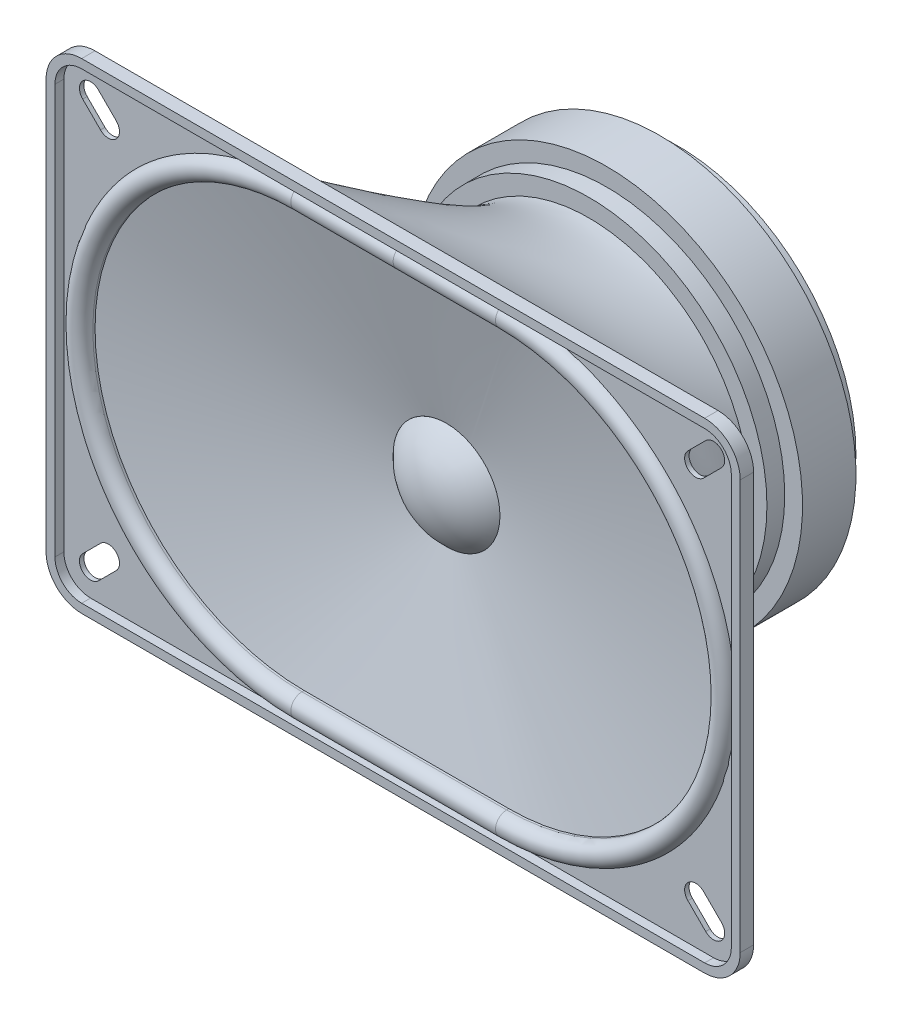
SolidWorks part; units mm, degrees
note: '?' marks a value the reader was unsure of.
ref_plane "Front Plane" through (0, 0, 0) normal (0, 0, 1) x (1, 0, 0)
ref_plane "Top Plane" through (0, 0, 0) normal (0, 1, 0) x (1, 0, 0)
ref_plane "Right Plane" through (0, 0, 0) normal (1, 0, 0) x (0, 0, -1)
sketch "Sketch1" plane through (0, 0, 0) normal (0, 0, 1) x (1, 0, 0)
  line L1 (-61.9125, -42.8625) -> (61.9125, -42.8625)
  line L2 (-61.9125, -42.8625) -> (-61.9125, 42.8625)
  line L3 (-61.9125, 42.8625) -> (61.9125, 42.8625)
  line L4 (61.9125, -42.8625) -> (61.9125, 42.8625)
  line L5 (-61.9125, -42.8625) -> (61.9125, 42.8625) construction
  line L6 (-61.9125, 42.8625) -> (61.9125, -42.8625) construction
  point P0 (0, 0)
  dimension "D1" = 123.825
  dimension "D2" = 85.725
extrude "Boss-Extrude1" add sketch "Sketch1" along normal blind 2.3813
fillet "Fillet1" radius 6.35 4 edges at (-61.9125, -42.8625, 1.1906) (61.9125, -42.8625, 1.1906) (61.9125, 42.8625, 1.1906) (-61.9125, 42.8625, 1.1906)
sketch "Sketch2" plane through (0, 0, 2.3813) normal (0, 0, 1) x (1, 0, 0)
  line L8 (-60.325, 36.5125) -> (-60.325, -36.5125)
  line L9 (-55.5625, -41.275) -> (55.5625, -41.275)
  line L10 (60.325, -36.5125) -> (60.325, 36.5125)
  line L11 (55.5625, 41.275) -> (-55.5625, 41.275)
  line L12 (-60.325, 36.5125) -> (-60.325, -36.5125)
  line L13 (-55.5625, -41.275) -> (55.5625, -41.275)
  line L14 (60.325, -36.5125) -> (60.325, 36.5125)
  line L15 (55.5625, 41.275) -> (-55.5625, 41.275)
  arc A8 (-60.325, -36.5125) -> (-55.5625, -41.275) centre (-55.5625, -36.5125) ccw
  arc A9 (55.5625, -41.275) -> (60.325, -36.5125) centre (55.5625, -36.5125) ccw
  arc A10 (60.325, 36.5125) -> (55.5625, 41.275) centre (55.5625, 36.5125) ccw
  arc A11 (-55.5625, 41.275) -> (-60.325, 36.5125) centre (-55.5625, 36.5125) ccw
  arc A12 (-60.325, -36.5125) -> (-55.5625, -41.275) centre (-55.5625, -36.5125) ccw
  arc A13 (55.5625, -41.275) -> (60.325, -36.5125) centre (55.5625, -36.5125) ccw
  arc A14 (60.325, 36.5125) -> (55.5625, 41.275) centre (55.5625, 36.5125) ccw
  arc A15 (-55.5625, 41.275) -> (-60.325, 36.5125) centre (-55.5625, 36.5125) ccw
  dimension "D1" = 1.5875
extrude "Cut-Extrude1" cut sketch "Sketch2" against normal blind 1.5875
sketch "Sketch3" plane through (0, 0, 0.7938) normal (0, 0, 1) x (1, 0, 0)
  line L0 (-18.2563, 0) -> (18.2563, 0) construction
  line L1 (29.6862, 0) -> (-29.6862, 0) construction
  line L2 (-18.2563, 38.8937) -> (18.2563, 38.8937)
  line L3 (-18.2563, -38.8937) -> (18.2563, -38.8937)
  line L4 (0, 0) -> (0, 56.4143) construction
  line L5 (0, -55) -> (0, 55) construction
  arc A0 (-18.2563, 38.8937) -> (-18.2563, -38.8937) centre (-18.2563, 0) ccw
  arc A1 (18.2563, -38.8937) -> (18.2563, 38.8937) centre (18.2563, 0) ccw
  point P5 (0, 0)
  dimension "D2" = 114.3
  dimension "D1" = 77.7875
extrude "Cut-Extrude2" cut sketch "Sketch3" against normal up to next
ref_plane "Plane1" through (0, 0, -48.4187) normal (0, 0, 1) x (1, 0, 0)
sketch "Sketch5" plane through (0, 0, 0) normal (1, 0, 0) x (0, 0, -1)
  line L0 (0, 0) -> (61.7456, 0) construction
  line L1 (29.6862, 0) -> (-29.6862, 0) construction
  line L2 (48.4187, 0) -> (48.4187, 9.525)
  line L3 (48.4187, 47.1487) -> (48.4187, -47.1487) construction
  line L4 (48.4187, 9.525) -> (7.1437, 9.525)
  line L5 (2.844, 0) -> (2.844, 33.6301) construction
  line L6 (2.844, 0) -> (48.4187, 0)
  arc A0 (2.844, 0) -> (7.1437, 9.525) centre (15.544, 0) cw
  dimension "D2" = 12.7
  dimension "D1" = 9.525
  dimension "D3" = 41.275
revolve "Revolve1" add sketch "Sketch5" angle 360 about L0
sketch "Sketch6" plane through (0, 0, -48.4187) normal (0, 0, 1) x (1, 0, 0)
  circle A0 centre (0, 0) radius 31.75
  dimension "D1" = 63.5
extrude "Boss-Extrude2" add sketch "Sketch6" along normal blind 15.875
ref_axis "Axis1" through (0, 0, -32.5437) along (0, 0, 1)?
sketch "Sketch10" plane through (0, 0, 0) normal (0, 0, 1) x (1, 0, 0)
  line L4 (-18.2563, -37.3062) -> (18.2562, -37.3062)
  line L5 (18.2563, 37.3062) -> (-18.2563, 37.3062)
  line L6 (-18.2563, -37.3062) -> (18.2562, -37.3062)
  line L7 (18.2563, 37.3062) -> (-18.2563, 37.3062)
  arc A4 (18.2562, -37.3062) -> (18.2563, 37.3062) centre (18.2563, 0) ccw
  arc A5 (-18.2563, 37.3062) -> (-18.2563, -37.3062) centre (-18.2563, 0) ccw
  arc A6 (18.2562, -37.3062) -> (18.2563, 37.3062) centre (18.2563, 0) ccw
  arc A7 (-18.2563, 37.3062) -> (-18.2563, -37.3062) centre (-18.2563, 0) ccw
  dimension "D1" = 1.5875
ref_plane "Plane3" through (0, 0, -7.1437) normal (0, 0, 1) x (1, 0, 0)
sketch "Sketch11" plane through (0, 0, -7.1437) normal (0, 0, 1) x (1, 0, 0)
  line L0 (0, 0) -> (-18.2563, -37.3062) construction
  line L1 (-18.2563, 37.3062) -> (0, 0) construction
  line L2 (0, 0) -> (18.2563, 37.3062) construction
  line L3 (18.2562, -37.3062) -> (0, 0) construction
  arc A2 (-4.1867, -8.5555) -> (4.1867, -8.5555) centre (0, 0) ccw
  circle A3 centre (0, 0) radius 9.525 construction
  circle A4 centre (0, 0) radius 9.525 construction
  arc A5 (-4.1867, -8.5555) -> (-4.1867, 8.5555) centre (0, 0) cw
  arc A6 (-4.1867, 8.5555) -> (4.1867, 8.5555) centre (0, 0) cw
  arc A7 (4.1867, 8.5555) -> (4.1867, -8.5555) centre (0, 0) cw
ref_plane "Plane4" through (0, 0, 0) normal (-0.8982, 0.4396, 0) x (0, 0, 1)
other "Boundary-Surface1"
sketch "Sketch14" plane through (0, 0, 0) normal (1, 0, 0) x (0, 0, -1)
  line L0 (0, 37.2999) -> (-0.3937, 37.2999)
  line L1 (-0.3937, 41.275) -> (1.312, 41.275) construction
  line L2 (-2.3813, 42.8625) -> (-2.3813, 36.5125) construction
  line L3 (0, 47.1487) -> (0, -47.1487) construction
  line L4 (-2.3813, 42.8625) -> (0, 42.8625) construction
  line L6 (0, 37.8079) -> (-0.3937, 37.8079)
  line L7 (0, 37.2999) -> (0, 37.8079)
  line L8 (-0.3937, 41.275) -> (-0.3937, 40.767)
  arc A0 (-0.3937, 37.2999) -> (-0.3937, 41.275) centre (-0.3937, 39.2874) cw
  arc A1 (-0.3937, 37.8079) -> (-0.3937, 40.767) centre (-0.3937, 39.2874) cw
  dimension "D1" = 1.5875
  dimension "D3" = 5.5626
  dimension "D4" = 0.508
sketch "Sketch16" plane through (0, 0, 0) normal (0, 0, 1) x (1, 0, 0)
  line L0 (-18.2563, 37.3062) -> (18.2563, 37.3062) construction
  line L1 (18.2562, -37.3062) -> (-18.2563, -37.3062) construction
  line L2 (-18.2563, 37.3062) -> (18.2563, 37.3062)
  line L3 (18.2562, -37.3062) -> (-18.2563, -37.3062)
  arc A0 (18.2562, -37.3062) -> (18.2563, 37.3062) centre (18.2563, 0) ccw construction
  arc A1 (-18.2563, 37.3062) -> (-18.2563, -37.3062) centre (-18.2563, 0) ccw construction
  arc A2 (18.2562, -37.3062) -> (18.2563, 37.3062) centre (18.2563, 0) ccw
  arc A3 (-18.2563, 37.3062) -> (-18.2563, -37.3062) centre (-18.2563, 0) ccw
surface "Surface-Sweep1"
sketch "Sketch17" plane through (0, 0, -32.5437) normal (0, 0, 1) x (1, 0, 0)
  circle A0 centre (0, 0) radius 28.575
  dimension "D1" = 57.15
sketch "Sketch18" plane through (0, 0, 0) normal (0, 0, -1) x (-1, 0, 0)
  line L4 (-18.2562, -40.4177) -> (18.2563, -40.4177)
  line L5 (18.2562, 40.4177) -> (-18.2563, 40.4177)
  line L6 (-18.2562, -40.4177) -> (18.2563, -40.4177)
  line L7 (18.2562, 40.4177) -> (-18.2563, 40.4177)
  arc A4 (18.2563, -40.4177) -> (18.2562, 40.4177) centre (18.2563, 0) ccw
  arc A5 (-18.2563, 40.4177) -> (-18.2562, -40.4177) centre (-18.2563, 0) ccw
  arc A6 (18.2563, -40.4177) -> (18.2562, 40.4177) centre (18.2563, 0) ccw
  arc A7 (-18.2563, 40.4177) -> (-18.2562, -40.4177) centre (-18.2563, 0) ccw
  dimension "D3" = 117.348
  dimension "D2" = 80.8355
  dimension "D1" = 1.524
other "Boundary-Surface2"
sketch "Sketch19" plane through (0, 0, -48.4187) normal (0, 0, -1) x (-1, 0, 0)
  circle A0 centre (0, 0) radius 34.925
  dimension "D1" = 69.85
extrude "Boss-Extrude3" add sketch "Sketch19" against normal blind 9.525 from offset 3.175 offset against normal yes
sketch "Sketch20" plane through (0, 0, 0.7938) normal (0, 0, 1) x (1, 0, 0)
  line L0 (-58.9301, 39.8801) -> (-49.7256, 30.6756) construction
  line L1 (-55.5625, 36.5125) -> (-52.3875, 33.3375) construction
  line L2 (-54.1593, 37.9157) -> (-50.9843, 34.7407)
  line L3 (-56.9657, 35.1093) -> (-53.7907, 31.9343)
  line L4 (-61.9125, 36.5125) -> (-61.9125, -36.5125) construction
  line L5 (0, 0) -> (0, 62.7849) construction
  line L6 (0, -29.2497) -> (0, 29.2497) construction
  line L7 (0, 0) -> (-103.8202, 0) construction
  line L8 (55.5625, 36.5125) -> (52.3875, 33.3375) construction
  line L9 (54.1593, 37.9157) -> (50.9843, 34.7407)
  line L10 (56.9657, 35.1093) -> (53.7907, 31.9343)
  line L11 (-55.5625, -36.5125) -> (-52.3875, -33.3375) construction
  line L12 (-54.1593, -37.9157) -> (-50.9843, -34.7407)
  line L13 (-56.9657, -35.1093) -> (-53.7907, -31.9343)
  line L14 (55.5625, -36.5125) -> (52.3875, -33.3375) construction
  line L15 (54.1593, -37.9157) -> (50.9843, -34.7407)
  line L16 (56.9657, -35.1093) -> (53.7907, -31.9343)
  arc A0 (-55.5625, 41.275) -> (-60.325, 36.5125) centre (-55.5625, 36.5125) ccw construction
  arc A1 (-54.1593, 37.9157) -> (-56.9657, 35.1093) centre (-55.5625, 36.5125) ccw
  arc A2 (-53.7907, 31.9343) -> (-50.9843, 34.7407) centre (-52.3875, 33.3375) ccw
  arc A3 (54.1593, 37.9157) -> (56.9657, 35.1093) centre (55.5625, 36.5125) cw
  arc A4 (53.7907, 31.9343) -> (50.9843, 34.7407) centre (52.3875, 33.3375) cw
  arc A5 (-54.1593, -37.9157) -> (-56.9657, -35.1093) centre (-55.5625, -36.5125) cw
  arc A6 (-53.7907, -31.9343) -> (-50.9843, -34.7407) centre (-52.3875, -33.3375) cw
  arc A7 (54.1593, -37.9157) -> (56.9657, -35.1093) centre (55.5625, -36.5125) ccw
  arc A8 (53.7907, -31.9343) -> (50.9843, -34.7407) centre (52.3875, -33.3375) ccw
  point P7 (-53.975, 34.925)
  point P22 (53.975, 34.925)
  point P29 (-53.975, -34.925)
  point P36 (53.975, -34.925)
  dimension "D1" = 6.35
  dimension "D4" = 3.9688
  dimension "D2" = 9.525
  dimension "D3" = 45
extrude "Cut-Extrude3" cut sketch "Sketch20" against normal up to next (0.7937 mm away)
